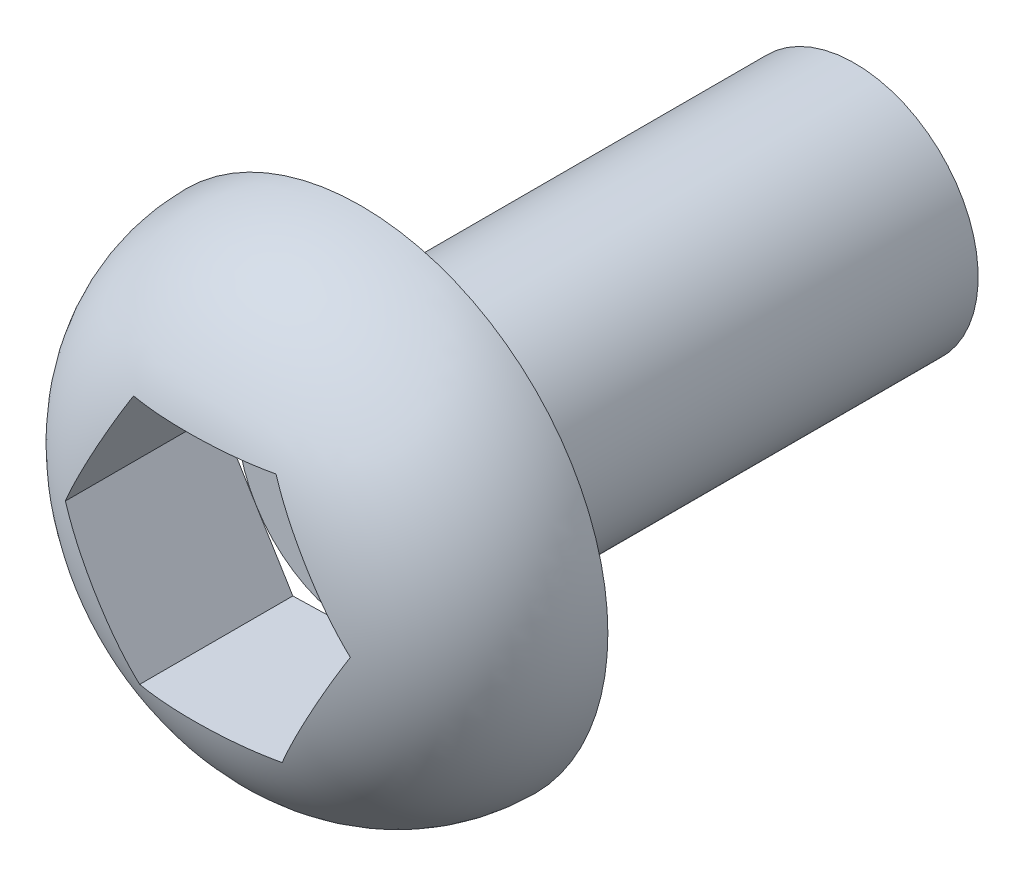
SolidWorks part; units mm, degrees
ref_plane "Front Plane" through (0, 0, 0) normal (0, 0, 1) x (1, 0, 0)
ref_plane "Top Plane" through (0, 0, 0) normal (0, 1, 0) x (1, 0, 0)
ref_plane "Right Plane" through (0, 0, 0) normal (1, 0, 0) x (0, 0, -1)
sketch "Sketch1" plane through (0, 0, 0) normal (0, 0, 1) x (1, 0, 0)
  circle A0 centre (0, 0) radius 3
  dimension "D1" = 6
extrude "Boss-Extrude1" add sketch "Sketch1" along normal blind 2
fillet "Fillet1" radius 2 1 edges at (3, 0, 2)
sketch "Sketch2" plane through (0, 0, 2) normal (0, 0, 1) x (1, 0, 0)
  line L1 (0.903, -1.478) -> (1.7315, 0.0431)
  line L2 (1.7315, 0.0431) -> (0.8285, 1.5211)
  line L3 (0.8285, 1.5211) -> (-0.903, 1.478)
  line L4 (-0.903, 1.478) -> (-1.7315, -0.0431)
  line L5 (-1.7315, -0.0431) -> (-0.8285, -1.5211)
  line L6 (-0.8285, -1.5211) -> (0.903, -1.478)
  circle A0 centre (0, 0) radius 1.5 construction
extrude "Cut-Extrude1" cut sketch "Sketch2" against normal blind 2
sketch "Sketch3" plane through (0, 0, 0) normal (0, 0, -1) x (-1, 0, 0)
  circle A0 centre (0, 0) radius 1.5
  dimension "D1" = 3
extrude "Boss-Extrude2" add sketch "Sketch3" along normal blind 6
